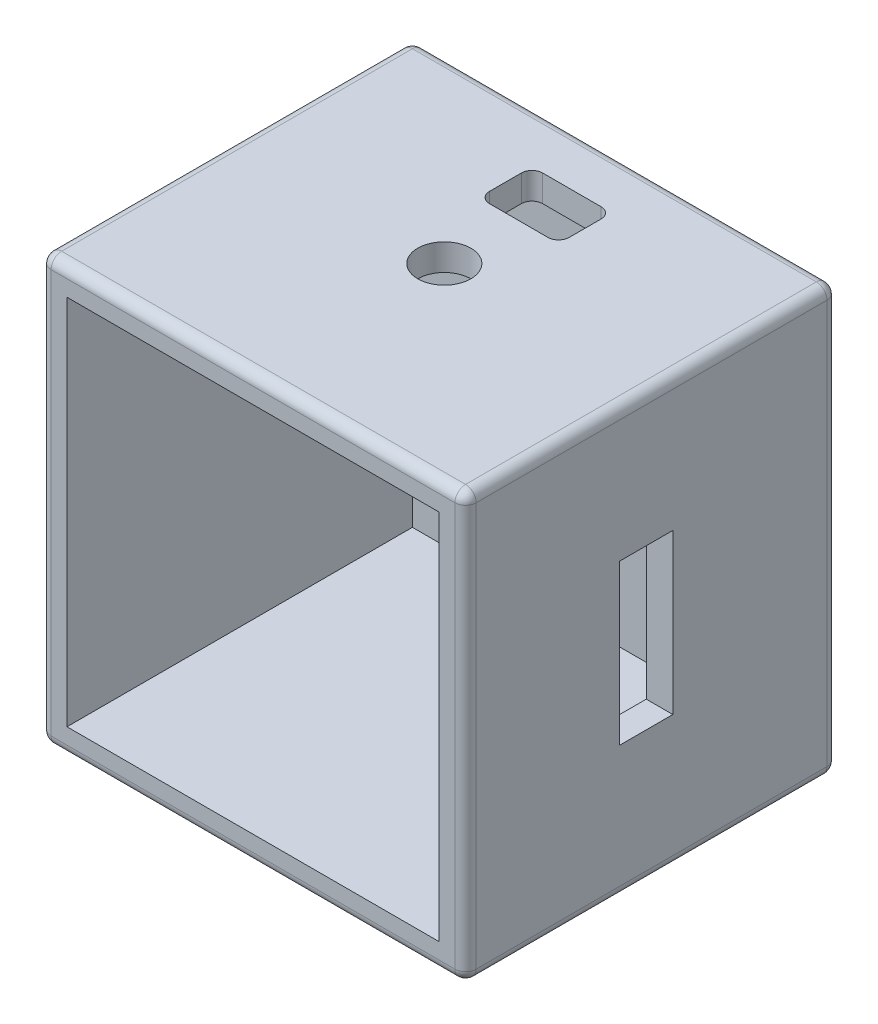
SolidWorks part; units mm, degrees
ref_plane "Спереди" through (0, 0, 0) normal (0, 0, 1) x (1, 0, 0)
ref_plane "Сверху" through (0, 0, 0) normal (0, 1, 0) x (1, 0, 0)
ref_plane "Справа" through (0, 0, 0) normal (1, 0, 0) x (0, 0, -1)
other "Configuration Table"
sketch "Эскиз1" plane through (0, 0, 0) normal (0, 0, 1) x (1, 0, 0)
  line L1 (40, -40) -> (-40, -40)
  line L2 (40, -40) -> (40, 40)
  line L3 (40, 40) -> (-40, 40)
  line L4 (-40, -40) -> (-40, 40)
  line L5 (40, -40) -> (-40, 40) construction
  line L6 (40, 40) -> (-40, -40) construction
  point P0 (0, 0)
  dimension "D1" = 80
  dimension "D2" = 80
extrude "Бобышка-Вытянуть1" add sketch "Эскиз1" along normal blind 70
sketch "Эскиз2" plane through (0, 0, 70) normal (0, 0, 1) x (1, 0, 0)
  line L0 (40, 40) -> (-40, 40) construction
  line L1 (35, -35) -> (-35, -35)
  line L2 (35, -35) -> (35, 35)
  line L3 (35, 35) -> (-35, 35)
  line L4 (-35, -35) -> (-35, 35)
  line L5 (35, -35) -> (-35, 35) construction
  line L6 (35, 35) -> (-35, -35) construction
  line L7 (40, -40) -> (40, 40) construction
  point P0 (0, 0)
  dimension "D1" = 5
  dimension "D2" = 5
extrude "Вырез-Вытянуть1" cut sketch "Эскиз2" against normal blind 65
fillet "Скругление1" radius 2 2 edges at (-40, -40, 35) (-40, 40, 35)
fillet "Скругление2" radius 2 7 edges at (1, -40, 0) (-39.4142, -39.4142, 0) (-40, 0, 0) (-39.4142, 39.4142, 0) (40, 0, 0) (40, 40, 35) (1, 40, 0)
fillet "Скругление3" radius 2 2 edges at (39.4142, -39.4142, 0.5858) (40, -40, 36)
sketch "Эскиз3" plane through (0, 40, 0) normal (0, 1, 0) x (1, 0, 0)
  line L0 (0, 0) -> (0, -46.1034) construction
  line L1 (38, -2) -> (-38, -2) construction
  line L2 (5.5, -20) -> (-5.5, -20)
  line L3 (7.5, -18) -> (7.5, -12)
  line L4 (5.5, -10) -> (-5.5, -10)
  line L5 (-7.5, -18) -> (-7.5, -12)
  line L6 (7.5, -20) -> (-7.5, -10) construction
  line L7 (7.5, -10) -> (-7.5, -20) construction
  arc A0 (7.5, -18) -> (5.5, -20) centre (5.5, -18) cw
  arc A1 (-7.5, -18) -> (-5.5, -20) centre (-5.5, -18) ccw
  arc A2 (7.5, -12) -> (5.5, -10) centre (5.5, -12) ccw
  arc A3 (-5.5, -10) -> (-7.5, -12) centre (-5.5, -12) ccw
  point P3 (0, -15)
  dimension "D4" = 2
  dimension "D1" = 8
  dimension "D2" = 15
  dimension "D3" = 10
extrude "Вырез-Вытянуть3" cut sketch "Эскиз3" against normal blind 10
sketch "Эскиз4" plane through (40, 0, 0) normal (1, 0, 0) x (0, 0, -1)
  line L0 (-70, 38) -> (-2, -38) construction
  line L1 (-2, 38) -> (-70, -38) construction
  line L3 (-31, -15) -> (-41, -15)
  line L4 (-31, -15) -> (-31, 15)
  line L5 (-31, 15) -> (-41, 15)
  line L6 (-41, -15) -> (-41, 15)
  line L7 (-31, -15) -> (-41, 15) construction
  line L8 (-31, 15) -> (-41, -15) construction
  point P8 (-36, 0)
  dimension "D1" = 10
  dimension "D2" = 30
extrude "Вырез-Вытянуть4" cut sketch "Эскиз4" against normal blind 10
sketch "Эскиз5" plane through (0, 40, 0) normal (0, 1, 0) x (1, 0, 0)
  line L0 (0, -2) -> (0, -34) construction
  line L1 (38, -2) -> (-38, -2) construction
  line L2 (-5.5, -20) -> (5.5, -20) construction
  circle A0 centre (0, -34) radius 5
  dimension "D1" = 10
  dimension "D2" = 14
extrude "Вырез-Вытянуть5" cut sketch "Эскиз5" against normal blind 10
fillet "Скругление4" radius 2 8 edges at (39.4142, -39.4142, 70) (-39.4142, -39.4142, 70) (-39.4142, 39.4142, 70) (39.4142, 39.4142, 70) (0, 40, 70) (-40, 0, 70) (0, -40, 70) (40, 0, 70)
